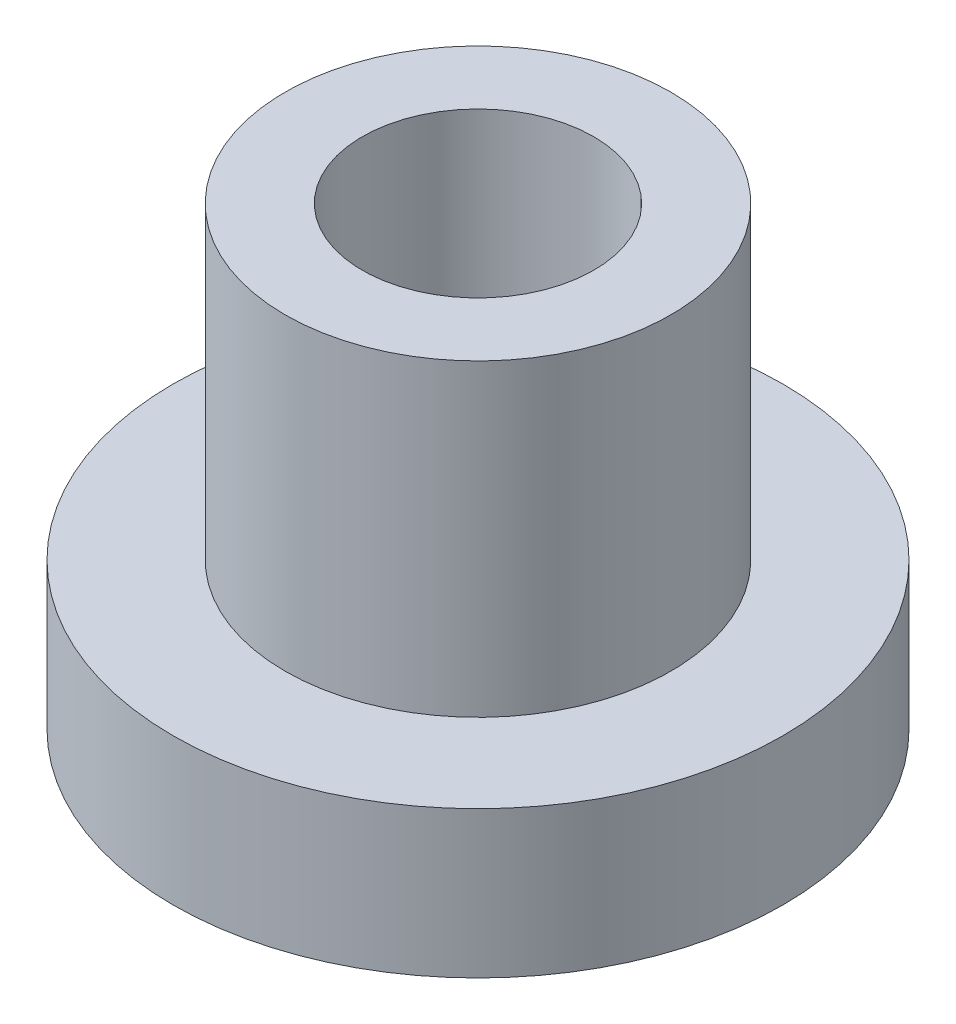
SolidWorks part; units mm, degrees
ref_plane "Front Plane" through (0, 0, 0) normal (0, 0, 1) x (1, 0, 0)
ref_plane "Top Plane" through (0, 0, 0) normal (0, 1, 0) x (1, 0, 0)
ref_plane "Right Plane" through (0, 0, 0) normal (1, 0, 0) x (0, 0, -1)
sketch "Sketch1" plane through (0, 0, 0) normal (0, 1, 0) x (1, 0, 0)
  circle A0 centre (0, 0) radius 3.95
  circle A1 centre (0, 0) radius 1.5
  dimension "D1" = 7.9
  dimension "D2" = 3
extrude "Boss-Extrude1" add sketch "Sketch1" along normal blind 1.9
sketch "Sketch2" plane through (0, 1.9, 0) normal (0, 1, 0) x (1, 0, 0)
  circle A0 centre (0, 0) radius 2.5
  circle A1 centre (0, 0) radius 1.5 construction
  circle A2 centre (0, 0) radius 1.5
  dimension "D1" = 5
extrude "Boss-Extrude2" add sketch "Sketch2" along normal blind 4
